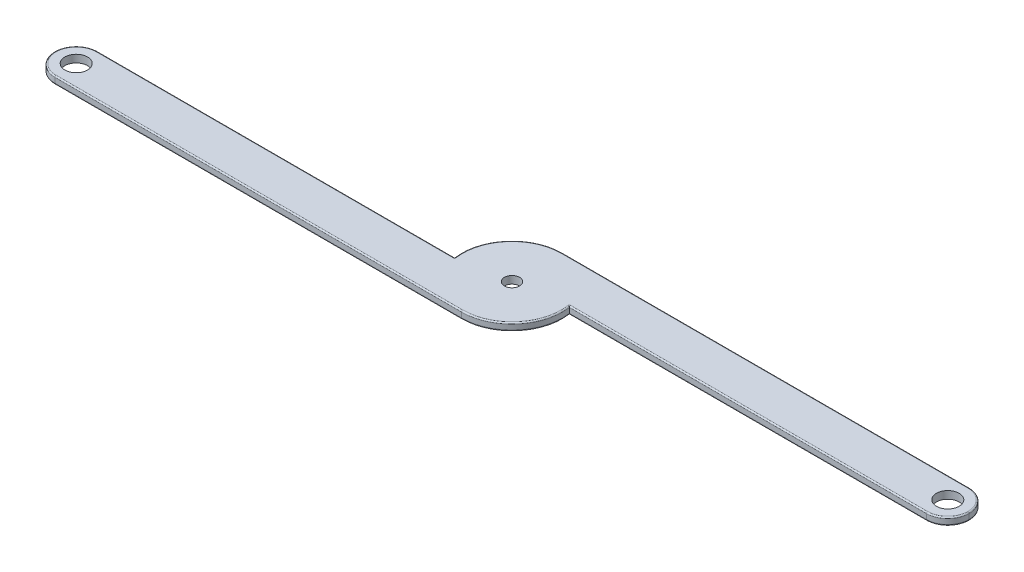
SolidWorks part; units mm, degrees
ref_plane "Front Plane" through (0, 0, 0) normal (0, 0, 1) x (1, 0, 0)
ref_plane "Top Plane" through (0, 0, 0) normal (0, 1, 0) x (1, 0, 0)
ref_plane "Right Plane" through (0, 0, 0) normal (1, 0, 0) x (0, 0, -1)
sketch "Sketch2" plane through (0, 0, 0) normal (0, 1, 0) x (1, 0, 0)
  line L0 (-1.5, 0) -> (10, 0) construction
  line L1 (0, 10) -> (80.751, 10)
  line L3 (9.8869, 1.5) -> (80.751, 1.5)
  line L4 (85, 5.751) -> (85, 5.749)
  line L9 (0, 1.5) -> (0, -1.5) construction
  line L11 (0, -10) -> (-80.751, -10)
  line L12 (-85, -5.751) -> (-85, -5.749)
  line L13 (-9.8869, -1.5) -> (-80.751, -1.5)
  arc A0 (0, 10) -> (-9.8869, -1.5) centre (0, 0) ccw
  circle A1 centre (0, 0) radius 1.5
  arc A2 (0, -10) -> (9.8869, 1.5) centre (0, 0) ccw
  arc A3 (85, 5.749) -> (80.751, 1.5) centre (80.751, 5.749) cw
  arc A4 (85, 5.751) -> (80.751, 10) centre (80.751, 5.751) ccw
  arc A5 (-80.751, -10) -> (-85, -5.751) centre (-80.751, -5.751) cw
  arc A6 (-85, -5.749) -> (-80.751, -1.5) centre (-80.751, -5.749) cw
  circle A7 centre (-80.751, -5.751) radius 2.25
  circle A8 centre (80.751, 5.751) radius 2.25
  point P18 (85, 10)
  dimension "D2" = 3
  dimension "D7" = 4.249
  dimension "D8" = 4.249
  dimension "D9" = 4.249
  dimension "D10" = 4.249
  dimension "D11" = 4.5
  dimension "D12" = 4.5
  dimension "D3" = 85
  dimension "D4" = 8.5
  dimension "D5" = 1.5
  dimension "D6" = 10
  dimension "D13" = 85
extrude "Boss-Extrude1" add sketch "Sketch2" along normal blind 1.5
fillet "Fillet1" radius 0.25 24 edges at (-45.3189, 0, 1.5) (-83.7555, 0, 2.7445) (-85, 0, 5.75) (-83.7555, 0, 8.7555) (-40.3755, 0, 10) (7.5829, 0, 6.5192) (45.3189, 0, -1.5) (83.7555, 0, -2.7445) (85, 0, -5.75) (83.7555, 0, -8.7555) (40.3755, 0, -10) (-7.5829, 0, -6.5192) (40.3755, 1.5, -10) (83.7555, 1.5, -8.7555) (85, 1.5, -5.75) (83.7555, 1.5, -2.7445) (45.3189, 1.5, -1.5) (7.5829, 1.5, 6.5192) (-40.3755, 1.5, 10) (-83.7555, 1.5, 8.7555) (-85, 1.5, 5.75) (-83.7555, 1.5, 2.7445) (-45.3189, 1.5, 1.5) (-7.5829, 1.5, -6.5192)
